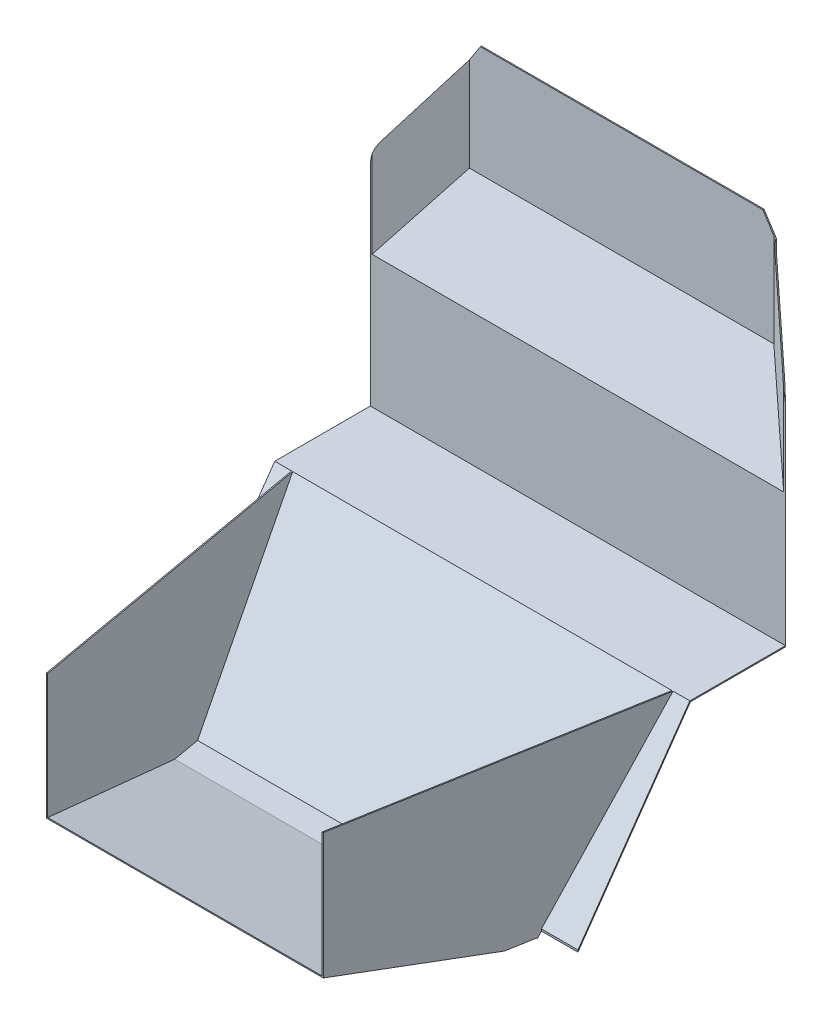
SolidWorks part; units mm, degrees
material "5052-H32"
ref_plane "Front Plane" through (0, 0, 0) normal (0, 0, 1) x (1, 0, 0)
ref_plane "Top Plane" through (0, 0, 0) normal (0, 1, 0) x (1, 0, 0)
ref_plane "Right Plane" through (0, 0, 0) normal (1, 0, 0) x (0, 0, -1)
sketch "Sketch1" plane through (0, 0, 0) normal (1, 0, 0) x (0, 0, -1)
  line L0 (622.162, 225.4) -> (412.0997, -74.6) construction
  line L1 (622.162, 225.4) -> (794.855, 225.4) construction
  line L2 (794.855, 225.4) -> (794.855, 464.4067) construction
  line L3 (794.855, 464.4067) -> (873.9068, 608.1653) construction
  line L4 (873.9068, 808.1653) -> (873.9068, 608.1653) construction
  line L5 (622.162, 225.4) -> (412.0997, -74.6)
  line L6 (622.162, 225.4) -> (794.855, 225.4)
  line L7 (794.855, 225.4) -> (794.855, 464.4067)
  line L8 (794.855, 464.4067) -> (873.9068, 608.1653)
  line L9 (873.9068, 808.1653) -> (873.9068, 608.1653)
ref_plane "Plane1" through (0, 808.1653, -873.9068) normal (0, -1, 0) x (-1, 0, 0)
sketch "Sketch2" plane through (0, 808.1653, -873.9068) normal (0, -1, 0) x (-1, 0, 0)
  line L0 (-375, 0) -> (375, 0) construction
  line L1 (-375, 2) -> (375, 2) construction
  line L2 (-375, 0) -> (375, 0)
  line L3 (-375, 2) -> (375, 2)
  line L4 (375, 2) -> (375, 0) construction
  line L5 (375, 2) -> (375, 0)
  line L6 (-375, 2) -> (-375, 0) construction
  line L7 (-375, 2) -> (-375, 0)
sweep "Sweep1" add profiles "Sketch2" path "Sketch1"
sketch "Sketch4" plane through (0, 0, 0) normal (0, 1, 0) x (1, 0, 0)
  line L0 (250, 84.8525) -> (-250, 84.8525) construction
  line L1 (375, 794.855) -> (-375, 794.855) construction
  line L2 (-250, 84.8525) -> (-375, 794.855) construction
  line L3 (375, 794.855) -> (250, 84.8525) construction
  line L4 (250, 84.8525) -> (-250, 84.8525)
  line L5 (375, 794.855) -> (-375, 794.855)
  line L6 (-250, 84.8525) -> (-375, 794.855)
  line L7 (375, 794.855) -> (250, 84.8525)
  line L8 (-375, 794.855) -> (-375, 84.8525)
  line L9 (375, 794.855) -> (375, 84.8525)
  line L10 (375, 84.8525) -> (250, 84.8525)
  line L11 (-375, 84.8525) -> (-250, 84.8525)
  line L12 (375, 420) -> (-375, 420) construction
  line L13 (375, 420) -> (-375, 420)
extrude "Cut-Extrude1" cut sketch "Sketch4" against normal through all both and the other way through all contours L8 L11 L6 | L10 L9 L7 region at (325.7321, 0, -235.1699) region at (-325.7321, 0, -235.1699)
ref_plane "Plane2" through (0, -74.6, 0) normal (0, 1, 0) x (1, 0, 0)
sketch "Sketch5" plane through (0, -74.6, 0) normal (0, 1, 0) x (1, 0, 0)
  line L0 (375, 794.855) -> (-375, 794.855) construction
  line L1 (250, 84.8525) -> (-250, 84.8525) construction
  line L2 (-250, 84.8525) -> (-375, 794.855) construction
  line L3 (375, 794.855) -> (250, 84.8525) construction
  line L4 (375, 794.855) -> (-375, 794.855)
  line L5 (250, 84.8525) -> (-250, 84.8525)
  line L6 (-250, 84.8525) -> (-375, 794.855)
  line L7 (375, 794.855) -> (250, 84.8525)
  line L9 (-307.9022, 413.738) -> (307.9022, 413.738) construction
  line L10 (-307.9022, 413.738) -> (307.9022, 413.738)
extrude "Boss-Extrude8" add sketch "Sketch5" along normal blind 2 contours L10 L6 L5 L7 region at (0, -74.6, -254.9842)
sketch "Sketch7" plane through (0, -74.6, 0) normal (0, 1, 0) x (1, 0, 0)
  line L0 (250, 84.8525) -> (-250, 84.8525) construction
  line L1 (375, 794.855) -> (250, 84.8525) construction
  line L2 (375, 794.855) -> (-375, 794.855) construction
  line L3 (-250, 84.8525) -> (-375, 794.855) construction
  line L4 (250, 84.8525) -> (-250, 84.8525)
  line L5 (375, 794.855) -> (250, 84.8525)
  line L6 (375, 794.855) -> (-375, 794.855)
  line L7 (-250, 84.8525) -> (-375, 794.855)
  line L8 (-372.9692, 794.855) -> (-247.9692, 84.8525)
  line L9 (372.9692, 794.855) -> (247.9692, 84.8525)
  dimension "D1" = 2
  dimension "D2" = 2
extrude "Boss-Extrude9" add sketch "Sketch7" along normal up to surface (300 mm away) contours L6 L9 L4 L5 | L8 L6 L7 L4 region at (311.4846, -74.6, -439.8537) region at (-311.4846, -74.6, -439.8537) up to face at (0, 225.4, -708.5085)
sketch "Sketch8" plane through (0, 0, 0) normal (1, 0, 0) x (0, 0, -1)
  line L0 (622.162, 225.4) -> (412.0997, -74.6) construction
  line L1 (622.162, 225.4) -> (794.855, 225.4) construction
  line L2 (622.162, 225.4) -> (412.0997, -74.6)
  line L3 (622.162, 225.4) -> (794.855, 225.4)
  line L4 (623.2031, 223.4) -> (794.855, 223.4)
  line L5 (623.2031, 223.4) -> (413.738, -75.7472)
  line L6 (794.855, 223.4) -> (794.855, -75.7472)
  line L7 (794.855, -75.7472) -> (413.738, -75.7472)
  dimension "D1" = 2
extrude "Cut-Extrude2" cut sketch "Sketch8" against normal through all both and the other way through all contours L7 L6 L4 L5 region at (0, 54.9334, -650.0483)
sketch "Sketch9" plane through (0, 808.1653, -873.9068) normal (0, -1, 0) x (-1, 0, 0)
  line L0 (-375, 0) -> (375, 0) construction
  line L1 (-375, 0) -> (375, 0)
  line L2 (375, -79.0518) -> (-375, -79.0518) construction
  line L4 (275, 0) -> (-275, 0)
  line L5 (-275, 0) -> (-371.8373, -79.0518)
  line L6 (275, 0) -> (371.8373, -79.0518)
  line L7 (-278.1627, 0) -> (-375, -79.0518)
  line L8 (-344.5964, -251.7448) -> (-250, -789.0544) construction
  line L9 (-375, -79.0518) -> (-371.8373, -79.0518)
  line L10 (-278.1627, 0) -> (-275, 0)
  line L11 (0, 0) -> (0, -251.9339) construction
  line L12 (375, -79.0518) -> (371.8373, -79.0518)
  line L13 (278.1627, 0) -> (275, 0)
  line L14 (278.1627, 0) -> (375, -79.0518)
  line L15 (375, -79.0518) -> (-375, -79.0518)
  line L16 (375, 0) -> (375, -79.0518)
  line L17 (-375, 0) -> (-375, -79.0518)
  line L18 (-278.1627, 0) -> (-278.1627, 2)
  line L19 (278.1627, 0) -> (278.1627, 2)
  line L22 (-375, 2) -> (-375, 0)
  line L23 (375, 2) -> (-375, 2)
  line L24 (375, 0) -> (375, 2)
  line L25 (-375, 0) -> (375, 0)
  line L26 (-375, 2) -> (-375, 0)
  line L27 (375, 2) -> (-375, 2)
  line L28 (375, 0) -> (375, 2)
  line L29 (-375, 0) -> (375, 0)
  point P7 (0, 0)
  dimension "D1" = 100
  dimension "D2" = 2
  dimension "D3" = 0
extrude "Boss-Extrude11" add sketch "Sketch9" along normal up to surface (343.7586 mm away) contours L14 L13 L6 L12 | L10 L7 L9 L5 region at (325, 808.1653, -834.3809) region at (-325, 808.1653, -834.3809) up to face at (0, 536.286, -834.3809)
extrude "Cut-Extrude4" cut sketch "Sketch9<5>" against normal through all and the other way through all contours L1 L28 L27 L19 | L16 L1 L14 | L18 L27 L26 L1 | L1 L17 L7 region at (326.5813, 808.1653, -874.9068) region at (342.7209, 808.1653, -847.5562) region at (-326.5813, 808.1653, -874.9068) region at (-342.7209, 808.1653, -847.5562)
sketch "Sketch9<5>" plane through (0, 808.1653, -873.9068) normal (0, -1, 0) x (-1, 0, 0) same geometry as "Sketch9"
sketch "Sketch10" plane through (0, 0, 0) normal (1, 0, 0) x (0, 0, -1)
  line L2 (84.8525, 0) -> (84.8525, -87.3)
  line L4 (84.8525, 225.4) -> (84.8525, -74.6) construction
  line L5 (84.8525, 225.4) -> (84.8525, -74.6) construction
  line L6 (420, -87.3) -> (84.8525, 0) construction
  line L7 (84.8525, -87.3) -> (420, -87.3)
  line L8 (412.0997, -74.6) -> (84.8525, -74.6) construction
  line L9 (412.0997, -74.6) -> (84.8525, -74.6)
  line L10 (420, -87.3) -> (84.8525, 0)
  line L12 (84.8525, -2.0667) -> (412.0657, -87.3)
  dimension "D1" = 2
extrude "Cut-Extrude5" cut sketch "Sketch10" against normal through all both and the other way through all contours L12 L2 L9 region at (0, -50.4222, -177.6717)
extrude "Boss-Extrude12" add sketch "Sketch10<3>" along normal up to surface and the other way up to surface contours L2 L12 L9 L10 region at (0, -37.8143, -226.0741) up to face at (297.1432, 11.7081, -352.6268) other way up to face at (-297.1432, 11.7081, -352.6268)
sketch "Sketch10<3>" plane through (0, 0, 0) normal (1, 0, 0) x (0, 0, -1) same geometry as "Sketch10"
sketch "Sketch11" plane through (0, 0, 0) normal (0, 0, 1) x (1, 0, 0)
  line L0 (-132.0915, 997.7058) -> (-362.0915, 643.5744) construction
  line L1 (132.0915, 997.7058) -> (362.0915, 643.5744) construction
  line L2 (-132.0915, 997.7058) -> (-362.0915, 643.5744)
  line L3 (132.0915, 997.7058) -> (362.0915, 643.5744)
  line L4 (375, 600) -> (375, 997.7058)
  line L5 (375, 997.7058) -> (132.0915, 997.7058)
  line L6 (-375, 600) -> (-375, 997.7058)
  line L7 (-375, 997.7058) -> (-132.0915, 997.7058)
  arc A0 (-362.0915, 643.5744) -> (-375, 600) centre (-295, 600) ccw construction
  arc A1 (375, 600) -> (362.0915, 643.5744) centre (295, 600) ccw construction
  arc A2 (-362.0915, 643.5744) -> (-375, 600) centre (-295, 600) ccw
  arc A3 (375, 600) -> (362.0915, 643.5744) centre (295, 600) ccw
extrude "Cut-Extrude6" cut sketch "Sketch11" against normal through all
